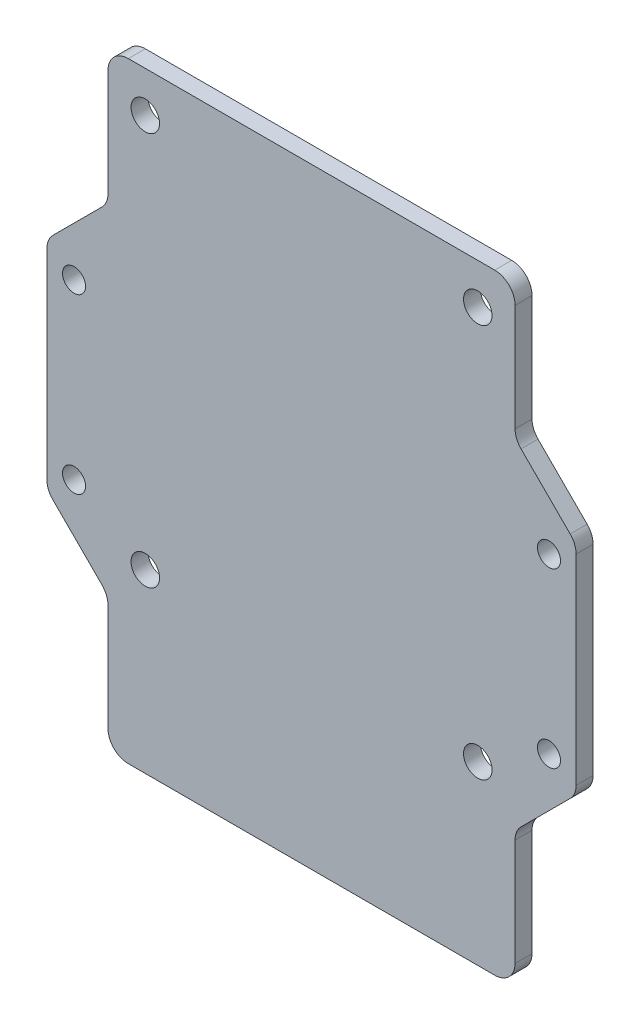
SolidWorks part; units mm, degrees
material "Thornel Mat VMA"
ref_plane "Front Plane" through (0, 0, 0) normal (0, 0, 1) x (1, 0, 0)
ref_plane "Top Plane" through (0, 0, 0) normal (0, 1, 0) x (1, 0, 0)
ref_plane "Right Plane" through (0, 0, 0) normal (1, 0, 0) x (0, 0, -1)
sketch "Sketch1" plane through (0, 0, 0) normal (0, 0, 1) x (1, 0, 0)
  line L0 (-39, -16) -> (-39, 16)
  line L5 (-30, 45) -> (30, 45)
  line L6 (-30, 45) -> (-30, -45)
  line L12 (-30, -45) -> (30, -45)
  line L17 (30, 45) -> (30, -45)
  line L19 (-30, 45) -> (30, -45) construction
  line L20 (-30, -45) -> (30, 45) construction
  line L21 (-39, 0) -> (39, 0) construction
  line L22 (-39, 16) -> (-30, 25)
  line L23 (-39, -16) -> (-30, -25)
  line L24 (0, 0) -> (0, 25) construction
  line L25 (39, -16) -> (30, -25)
  line L26 (39, 16) -> (30, 25)
  line L27 (39, -16) -> (39, 16)
  point P0 (0, 0)
  dimension "D1" = 60
  dimension "D2" = 90
  dimension "D3" = 9
  dimension "D4" = 16
  dimension "D5" = 135
extrude "Boss-Extrude1" add sketch "Sketch1" along normal mid plane 2.5 contours L5 | L17 L5 L6 L12 | L0 L23 L6 L22 | L25 L27 L26 L17 region at (-34.1707, 0, 0) region at (0, 0, 0) region at (34.1707, 0, 0)
fillet "Fillet1" radius 3 12 edges at (30, 45, 0) (30, -45, 0) (-30, -45, 0) (-30, 45, 0) (30, 25, 0) (39, 16, 0) (39, -16, 0) (30, -25, 0) (-30, -25, 0) (-39, -16, 0) (-39, 16, 0) (-30, 25, 0)
hole_wizard "Ø4.2 (4.2) Diameter Hole1" positions "Sketch2" profile "Sketch3" hole size "Ø4.2" standard "ANSI Metric" end condition through all
sketch "Sketch2" plane through (0, 0, -1.25) normal (0, 0, -1) x (-1, 0, 0)
  point P0 (-24.5, -19)
  point P3 (24.5, -19)
  point P6 (24.5, 39)
  point P9 (-24.5, 39)
sketch "Sketch3" plane through (24.5, -19, -1.25) normal (1, 0, 0) x (0, 1, 0)
  line L0 (0, 0) -> (0, 2.5)
  line L1 (0, 2.5) -> (2.1, 2.5)
  line L2 (2.1, 2.5) -> (2.1, 0)
  line L5 (2.1, 0) -> (0, 0)
  line L11 (0, -6.35) -> (0, 107.95) construction
  dimension "Thru Hole Dia." = 4.2
  dimension "Thru Hole Depth" = 2.5
hole_wizard "M3 Clearance Hole1" positions "Sketch4" profile "Sketch5" hole size "M3" standard "ANSI Metric" end condition through all
sketch "Sketch4" plane through (0, 0, -1.25) normal (0, 0, -1) x (-1, 0, 0)
  point P0 (-35, 12.75)
  point P3 (-35, -12.75)
  point P6 (35, -12.75)
  point P9 (35, 12.75)
sketch "Sketch5" plane through (35, 12.75, -1.25) normal (1, 0, 0) x (0, 1, 0)
  line L0 (0, 0) -> (0, 2.5)
  line L1 (0, 2.5) -> (1.7, 2.5)
  line L2 (1.7, 2.5) -> (1.7, 0)
  line L5 (1.7, 0) -> (0, 0)
  line L11 (0, -6.35) -> (0, 107.95) construction
  dimension "Thru Hole Dia." = 3.4
  dimension "Thru Hole Depth" = 2.5
